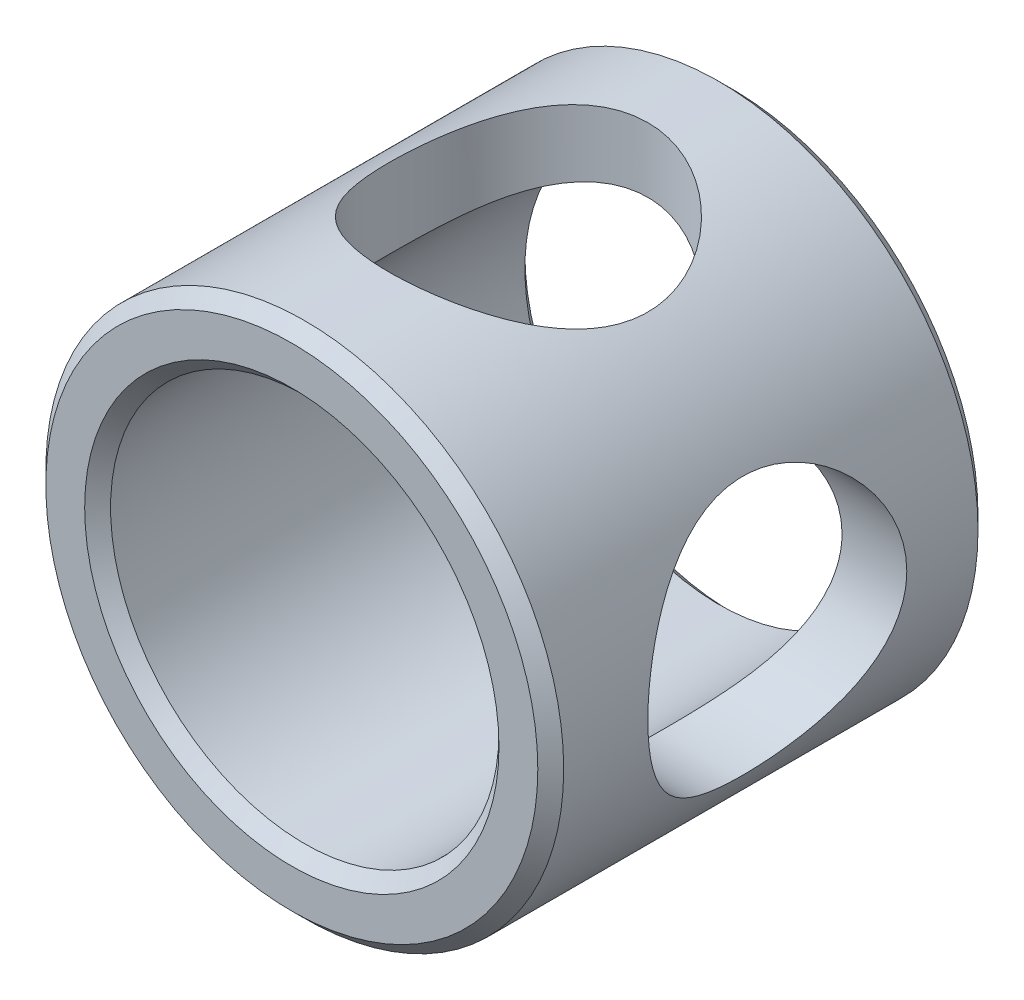
SolidWorks part; units mm, degrees
note: '?' marks a value the reader was unsure of.
material "Brass"
ref_plane "Front Plane" through (0, 0, 0) normal (0, 0, 1) x (1, 0, 0)
ref_plane "Top Plane" through (0, 0, 0) normal (0, 1, 0) x (1, 0, 0)
ref_plane "Right Plane" through (0, 0, 0) normal (1, 0, 0) x (0, 0, -1)
sketch "Sketch1" plane through (0, 0, 0) normal (0, 0, 1) x (1, 0, 0)
  circle A0 centre (0, 0) radius 4
  circle A1 centre (0, 0) radius 3
  dimension "D1" = 8
  dimension "D2" = 6
extrude "Boss-Extrude1" add sketch "Sketch1" along normal blind 6.8
chamfer "Chamfer1" distance 0.2 angle 45 4 edges at (3, 0, 0) (4, 0, 0) (4, 0, 6.8) (3, 0, 6.8)
ref_plane "Plane1" through (4, 0, 0) normal (1, 0, 0) x (0, 0, -1)
sketch "Sketch2" plane through (4, 0, 0) normal (1, 0, 0) x (0, 0, -1)
  line L0 (-6.8, 0) -> (-3.3, 0) construction
  line L1 (-6.8, 3.8) -> (-6.8, -3.8) construction
  circle A0 centre (-3.3, 0) radius 2
  dimension "D2" = 4
  dimension "D1" = 3.5
extrude "Cut-Extrude1" cut sketch "Sketch2" against normal up to next
ref_axis "Axis1" through (0, 0, 6.6) along (0, 0, -1)?
pattern_circular "CirPattern1" count 2 every 90 about axis through (0, 0, 6.6) along (0, 0, -1) of "Cut-Extrude1"
